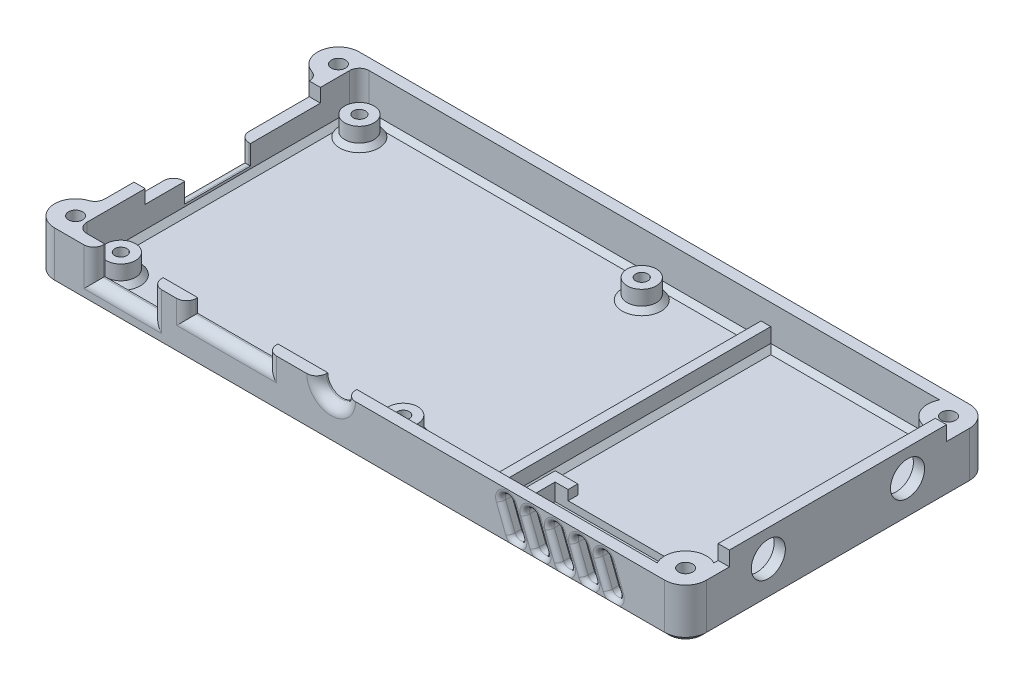
SolidWorks part; units mm, degrees
ref_plane "Front Plane" through (0, 0, 0) normal (0, 0, 1) x (1, 0, 0)
ref_plane "Top Plane" through (0, 0, 0) normal (0, 1, 0) x (1, 0, 0)
ref_plane "Right Plane" through (0, 0, 0) normal (1, 0, 0) x (0, 0, -1)
sketch "Sketch1" plane through (0, 0, 0) normal (0, 1, 0) x (1, 0, 0)
  line L0 (-71.5618, 3.106) -> (51.4382, 3.106) construction
  line L1 (-71.5618, 31.106) -> (51.4382, 31.106)
  line L2 (-71.5618, 31.106) -> (-71.5618, -24.894)
  line L3 (-71.5618, -24.894) -> (51.4382, -24.894)
  line L4 (51.4382, 31.106) -> (51.4382, -24.894)
  line L5 (-60.6618, -24.894) -> (-60.6618, -31.6828) construction
  line L6 (-68.0618, 27.606) -> (-10.0618, 27.606)
  line L7 (-68.0618, 27.606) -> (-68.0618, -21.394)
  line L8 (-68.0618, -21.394) -> (-10.0618, -21.394)
  line L9 (-10.0618, 27.606) -> (-10.0618, -21.394)
  line L10 (-39.5618, -24.894) -> (-39.5618, -31.6828) construction
  line L11 (-18.0618, -24.894) -> (-18.0618, -31.6828) construction
  line L12 (-65.4118, -26.5648) -> (-55.9118, -26.5648) construction
  line L13 (-48.0618, -26.5648) -> (-31.0618, -26.5648) construction
  line L14 (-22.0618, -26.5648) -> (-14.0618, -26.5648) construction
  line L15 (-72.5618, 9.606) -> (-72.5618, -3.394) construction
  line L16 (-71.5618, 3.106) -> (-72.5618, 3.106) construction
  dimension "D1" = 123
  dimension "D2" = 56
  dimension "D3" = 49
  dimension "D4" = 58
  dimension "D5" = 3.5
  dimension "D6" = 3.5
  dimension "D7" = 10.9
  dimension "D8" = 32
  dimension "D9" = 53.5
  dimension "D10" = 2
  dimension "D11" = 13
  dimension "D12" = 9.5
  dimension "D13" = 17
  dimension "D14" = 8
sketch "Sketch3" plane through (0, 0, 0) normal (0, 1, 0) x (1, 0, 0)
  line L4 (54.7382, 34.406) -> (-74.8618, 34.406)
  line L5 (-74.8618, 34.406) -> (-74.8618, -28.194)
  line L6 (-74.8618, -28.194) -> (54.7382, -28.194)
  line L7 (54.7382, -28.194) -> (54.7382, 34.406)
  line L8 (52.4382, 32.106) -> (-72.5618, 32.106)
  line L9 (52.4382, -25.894) -> (52.4382, 32.106)
  line L10 (-72.5618, -25.894) -> (52.4382, -25.894)
  line L11 (-72.5618, 32.106) -> (-72.5618, -25.894)
  line L12 (52.4382, 32.106) -> (-72.5618, 32.106)
  line L13 (52.4382, -25.894) -> (52.4382, 32.106)
  line L14 (-72.5618, -25.894) -> (52.4382, -25.894)
  line L15 (-72.5618, 32.106) -> (-72.5618, -25.894)
  line L16 (-10.0618, 3.106) -> (-10.0618, 34.406) construction
  line L17 (-71.5618, 3.106) -> (51.4382, 3.106) construction
  line L20 (-74.8618, 3.106) -> (52.7382, 3.106) construction
  line L25 (54.7382, -28.194) -> (54.7382, 34.406) construction
  line L26 (52.4382, -25.894) -> (52.4382, 32.106) construction
  dimension "D1" = 1
  dimension "D2" = 2.3
extrude "Boss-Extrude1" add sketch "Sketch3" along normal blind 10.3
sketch "Sketch5" plane through (0, 0, 0) normal (0, 1, 0) x (1, 0, 0)
  line L1 (-72.5618, 32.106) -> (52.4382, 32.106)
  line L2 (-72.5618, 32.106) -> (-72.5618, -25.894)
  line L3 (-72.5618, -25.894) -> (52.4382, -25.894)
  line L4 (52.4382, 32.106) -> (52.4382, -25.894)
extrude "Boss-Extrude2" add sketch "Sketch5" along normal blind 2
sketch "Sketch6" plane through (0, 2, 0) normal (0, 1, 0) x (1, 0, 0)
  circle A0 centre (-68.0618, 27.606) radius 3
  circle A1 centre (-68.0618, -21.394) radius 3
  circle A2 centre (-10.0618, -21.394) radius 3
  circle A3 centre (-10.0618, 27.606) radius 3
extrude "Boss-Extrude3" add sketch "Sketch6" along normal blind 4
hole_wizard "Ø2.5 (2.5) Diameter Hole1" positions "Sketch8" profile "Sketch9" hole size "Ø2.5" standard "ANSI Metric"
sketch "Sketch8" plane through (0, 6, 0) normal (0, 1, 0) x (1, 0, 0)
  point P0 (-68.0618, 27.606)
  point P3 (-10.0618, 27.606)
  point P6 (-10.0618, -21.394)
  point P9 (-68.0618, -21.394)
sketch "Sketch9" plane through (-68.0618, 6, -27.606) normal (1, 0, 0) x (0, 0, 1)
  line L0 (0, 0) -> (0, 8.7511)
  line L1 (0, 8.7511) -> (1.25, 8)
  line L2 (1.25, 8) -> (1.25, 0)
  line L5 (1.25, 0) -> (0, 0)
  line L10 (0, 8.7511) -> (-1.25, 8) construction
  line L11 (0, -6.35) -> (0, 107.95) construction
  dimension "Hole Dia." = 2.5
  dimension "Hole Depth" = 8
  dimension "Drill Angle" = 118
sketch "Sketch10" plane through (0, 2, 0) normal (0, 1, 0) x (1, 0, 0)
  line L0 (52.4382, 32.106) -> (-72.5618, 32.106) construction
  line L1 (9.9382, 32.106) -> (11.9382, 32.106)
  line L2 (9.9382, 32.106) -> (9.9382, -25.894)
  line L3 (9.9382, -25.894) -> (11.9382, -25.894)
  line L4 (11.9382, 32.106) -> (11.9382, -25.894)
  line L5 (-72.5618, -25.894) -> (52.4382, -25.894) construction
  line L6 (-10.0618, 27.606) -> (-10.0618, -21.394) construction
  dimension "D1" = 2
  dimension "D2" = 20
extrude "Boss-Extrude4" add sketch "Sketch10" along normal blind 4
sketch "Sketch11" plane through (0, 0, 28.194) normal (0, 0, 1) x (1, 0, 0)
  line L0 (-74.8618, 10.3) -> (-74.8618, 0) construction
  line L1 (-66.8618, 10.3) -> (-54.8618, 10.3)
  line L2 (-66.8618, 10.3) -> (-66.8618, 4.5)
  line L3 (-66.8618, 4.5) -> (-54.8618, 4.5)
  line L4 (-54.8618, 10.3) -> (-54.8618, 4.5)
  line L5 (-74.8618, 0) -> (54.7382, 0) construction
  line L6 (-60.8618, 10.3) -> (-60.6618, 0) construction
  line L7 (-65.4118, 0) -> (-55.9118, 0) construction
  line L9 (-47.778, 10.3) -> (-31.278, 10.3)
  line L10 (-47.778, 10.3) -> (-47.778, 7.5)
  line L11 (-47.778, 7.5) -> (-31.278, 7.5)
  line L12 (-31.278, 10.3) -> (-31.278, 7.5)
  line L13 (-68.0618, 0) -> (-10.0618, 0) construction
  line L14 (-39.5618, 0) -> (-39.528, 10.3) construction
  line L15 (-48.0618, 0) -> (-31.0618, 0) construction
  line L16 (-18.0618, 0) -> (-18.0618, 10.3) construction
  line L17 (-22.0618, 0) -> (-14.0618, 0) construction
  line L18 (-74.8618, 10.3) -> (54.7382, 10.3) construction
  circle A0 centre (-18.0618, 10.3) radius 3
  dimension "D5" = 6
  dimension "D1" = 4.5
  dimension "D2" = 12
  dimension "D3" = 7.5
  dimension "D4" = 16.5
  dimension "D6" = 8
extrude "Cut-Extrude1" cut sketch "Sketch11" against normal up to next
sketch "Sketch12" plane through (-74.8618, 0, 0) normal (-1, 0, 0) x (0, 0, 1)
  line L0 (-3.106, 0) -> (-3.106, 10.3) construction
  line L1 (-27.606, 0) -> (21.394, 0) construction
  line L2 (-34.406, 10.3) -> (28.194, 10.3) construction
  line L4 (-9.7329, 10.3) -> (3.7671, 10.3)
  line L5 (-9.7329, 10.3) -> (-9.7329, 3.5)
  line L6 (-9.7329, 3.5) -> (3.7671, 3.5)
  line L7 (3.7671, 10.3) -> (3.7671, 3.5)
  line L8 (-24.106, 10.3) -> (11.894, 10.3)
  line L9 (-24.106, 10.3) -> (-24.106, 7.5)
  line L10 (-24.106, 7.5) -> (11.894, 7.5)
  line L11 (11.894, 10.3) -> (11.894, 7.5)
  dimension "D1" = 13.5
  dimension "D2" = 3.5
  dimension "D3" = 7.5
  dimension "D4" = 36
extrude "Cut-Extrude2" cut sketch "Sketch12" against normal up to next contours L10 L11 L8 L9 | L7 L6 L5 L4
fillet "Fillet6" radius 2 1 edges at (52.4382, 6.15, -32.106)
fillet "Fillet8" radius 2 2 edges at (-72.5618, 6.15, 25.894) (-72.5618, 6.15, -32.106)
chamfer "Chamfer1" distance 1 angle 45 4 edges at (-68.0618, 2, 24.394) (-10.0618, 2, 24.394) (-10.0618, 2, -24.606) (-68.0618, 2, -24.606)
fillet "Fillet9" radius 2 9 edges at (-74.8618, 5.5, -9.7329) (-74.8618, 3.5, -2.9829) (-74.8618, 5.5, 3.7671) (-18.0618, 7.3, 28.194) (-31.278, 8.9, 28.194) (-47.778, 8.9, 28.194) (-39.528, 7.5, 28.194) (-54.8618, 7.4, 28.194) (-60.8618, 4.5, 28.194)
sketch "Sketch13" plane through (54.7382, 0, -61.1442) normal (1, 0, 0) x (0, 0, -1)
  line L0 (-89.3382, 10.3) -> (-89.3382, 0) construction
  line L1 (-26.7382, 10.3) -> (-26.7382, 0) construction
  circle A0 centre (-72.3382, 7.7223) radius 3.5
  circle A1 centre (-43.7382, 7.7223) radius 3.5
  dimension "D1" = 17
  dimension "D2" = 17
sketch "Sketch17" plane through (0, 0, 0) normal (0, 1, 0) x (1, 0, 0)
  line L0 (-74.8618, 34.406) -> (-74.8618, 24.106) construction
  line L1 (-74.8618, 34.406) -> (-74.8618, 25.806)
  line L2 (-74.8618, 25.806) -> (-74.659, 25.9406)
  line L3 (-74.8618, -19.594) -> (-74.8618, -28.194)
  line L4 (-74.8618, -28.194) -> (-74.659, -28.0594)
  arc A0 (-74.8618, -19.594) -> (-74.8618, -28.194) centre (-74.8618, -23.894) ccw
  arc A1 (-74.8618, 34.406) -> (-74.8618, 25.806) centre (-74.8618, 30.106) ccw
extrude "Boss-Extrude6" add sketch "Sketch17" along normal up to vertex (10.3 mm away) contours L1 A1 | L3 A0 region at (-76.6867, 0, -30.106) region at (-76.6867, 0, 23.894) up to point (-74.8618, 10.3, 28.194)
hole_wizard "Ø2.9 (2.9) Diameter Hole2" positions "Sketch19" profile "Sketch18" hole size "Ø2.9" standard "ANSI Metric" end condition up to next
sketch "Sketch19" plane through (0, 10.3, 0) normal (0, 1, 0) x (1, 0, 0)
  point P0 (-74.8618, 30.106)
sketch "Sketch18" plane through (-74.8618, 10.3, -30.106) normal (1, 0, 0) x (0, 0, 1)
  line L0 (0, 0) -> (0, 10.3)
  line L1 (0, 10.3) -> (1.45, 10.3)
  line L2 (1.45, 10.3) -> (1.45, 0)
  line L5 (1.45, 0) -> (0, 0)
  line L11 (0, -6.35) -> (0, 107.95) construction
  dimension "Thru Hole Dia." = 2.9
  dimension "Thru Hole Depth" = 10.3
hole_wizard "Ø2.9 (2.9) Diameter Hole1" positions "Sketch21" profile "Sketch20" hole size "Ø2.9" standard "ANSI Metric" end condition up to next
sketch "Sketch21" plane through (0, 10.3, 0) normal (0, 1, 0) x (1, 0, 0)
  point P0 (-74.8618, -23.894)
sketch "Sketch20" plane through (-74.8618, 10.3, 23.894) normal (1, 0, 0) x (0, 0, 1)
  line L0 (0, 0) -> (0, 10.3)
  line L1 (0, 10.3) -> (1.45, 10.3)
  line L2 (1.45, 10.3) -> (1.45, 0)
  line L5 (1.45, 0) -> (0, 0)
  line L11 (0, -6.35) -> (0, 107.95) construction
  dimension "Thru Hole Dia." = 2.9
  dimension "Thru Hole Depth" = 10.3
sketch "Sketch24" plane through (0, 2, 0) normal (0, 1, 0) x (1, 0, 0)
  line L0 (11.9382, 3.106) -> (61.5789, 3.106) construction
  line L1 (11.9382, -25.894) -> (11.9382, 32.106) construction
  line L2 (54.7382, -28.194) -> (54.7382, 34.406) construction
  circle A0 centre (50.4382, -23.894) radius 4.3
  circle A1 centre (50.4382, 30.106) radius 4.3
  dimension "D1" = 4.3
extrude "Boss-Extrude7" add sketch "Sketch24" along normal up to surface (8.3 mm away) up to face at (-74.8618, 10.3, 25.344)
hole_wizard "Ø2.9 (2.9) Diameter Hole5" positions "Sketch31" profile "Sketch30" hole size "Ø2.9" standard "ANSI Metric" end condition up to next
sketch "Sketch31" plane through (0, 10.3, 0) normal (0, 1, 0) x (1, 0, 0)
  point P0 (50.4382, -23.894)
sketch "Sketch30" plane through (50.4382, 10.3, 23.894) normal (1, 0, 0) x (0, 0, 1)
  line L0 (0, 0) -> (0, 10.3)
  line L1 (0, 10.3) -> (1.45, 10.3)
  line L2 (1.45, 10.3) -> (1.45, 0)
  line L5 (1.45, 0) -> (0, 0)
  line L11 (0, -6.35) -> (0, 107.95) construction
  dimension "Thru Hole Dia." = 2.9
  dimension "Thru Hole Depth" = 10.3
hole_wizard "Ø2.9 (2.9) Diameter Hole4" positions "Sketch28" profile "Sketch27" hole size "Ø2.9" standard "ANSI Metric" end condition up to next
sketch "Sketch28" plane through (0, 10.3, 0) normal (0, 1, 0) x (1, 0, 0)
  point P0 (50.4382, 30.106)
sketch "Sketch27" plane through (50.4382, 10.3, -30.106) normal (1, 0, 0) x (0, 0, 1)
  line L0 (0, 0) -> (0, 10.3)
  line L1 (0, 10.3) -> (1.45, 10.3)
  line L2 (1.45, 10.3) -> (1.45, 0)
  line L5 (1.45, 0) -> (0, 0)
  line L11 (0, -6.35) -> (0, 107.95) construction
  dimension "Thru Hole Dia." = 2.9
  dimension "Thru Hole Depth" = 10.3
fillet "Fillet10" radius 4.3 1 edges at (54.7382, 5.15, -34.406)
fillet "Fillet18" radius 2 2 edges at (-74.8618, 5.15, 19.594) (-74.8618, 5.15, -25.806)
chamfer "Chamfer3" distance 1 angle 45 9 edges at (53.4788, 0, -33.1466) (-12.2118, 0, -34.406) (54.7382, 0, -0.956) (-79.1058, 0, -30.7975) (-75.2385, 0, -25.3002) (-74.8618, 0, -3.106) (-75.2385, 0, 19.0883) (-79.1058, 0, 24.5855) (-10.0618, 0, 28.194)
fillet "Fillet19" radius 2 1 edges at (-66.8618, 6.4, 28.194)
fillet "Fillet20" radius 4.3 1 edges at (54.7382, 5.65, 28.194)
chamfer "Chamfer5" distance 1 angle 45 8 edges at (-72.5618, 2, -3.106) (-71.976, 2, 25.3082) (-71.976, 2, -31.5202) (-30.3118, 2, 25.894) (-30.3118, 2, -32.106) (9.9382, 2, -3.106) (11.9382, 2, -3.106) (29.2849, 2, -32.106)
chamfer "Chamfer6" distance 1 angle 45 1 edges at (52.4382, 2, -3.106)
sketch "Sketch29" plane through (0, 10.3, 0) normal (0, 1, 0) x (1, 0, 0)
  line L0 (52.4382, -20.0874) -> (52.4382, 26.2994) construction
  line L1 (52.4382, 25.406) -> (54.7382, 25.406)
  line L2 (52.4382, 25.406) -> (52.4382, -19.194)
  line L3 (52.4382, -19.194) -> (54.7382, -19.194)
  line L4 (54.7382, 25.406) -> (54.7382, -19.194)
  line L5 (54.7382, -23.894) -> (54.7382, 30.106) construction
  line L6 (50.4382, 34.406) -> (-74.8618, 34.406) construction
  line L7 (-13.0618, -28.194) -> (50.4382, -28.194) construction
  dimension "D1" = 9
  dimension "D2" = 9
extrude "Boss-Extrude8" add sketch "Sketch29" along normal blind 3
extrude "Cut-Extrude3" cut sketch "Sketch13" against normal up to next
sketch "Sketch32" plane through (0, 2, 0) normal (0, 1, 0) x (1, 0, 0)
  line L0 (12.9382, -25.894) -> (46.6317, -25.894) construction
  line L1 (15.4382, -15.694) -> (45.5382, -15.694)
  line L2 (15.4382, -15.694) -> (15.4382, -25.894)
  line L3 (15.4382, -25.894) -> (45.5382, -25.894)
  line L4 (45.5382, -15.694) -> (45.5382, -25.894)
  line L5 (-72.5618, -23.894) -> (-72.5618, 30.106) construction
  dimension "D1" = 10.2
  dimension "D2" = 30.1
  dimension "D3" = 88
extrude "Cut-Extrude4" cut sketch "Sketch32" against normal blind 1.5
sketch "Sketch33" plane through (0, 2, 0) normal (0, 1, 0) x (1, 0, 0)
  line L0 (15.4382, -15.694) -> (15.4382, -25.894)
  line L2 (15.4382, -25.894) -> (13.4382, -25.894)
  line L3 (12.9382, -25.894) -> (15.4382, -25.894) construction
  line L4 (47.5382, -13.694) -> (47.5382, -20.8822)
  line L5 (47.5382, -20.8822) -> (45.5382, -20.8822)
  line L6 (45.5382, -25.894) -> (45.5382, -20.7012) construction
  line L7 (45.5382, -20.8822) -> (45.5382, -15.694)
  line L8 (30.4882, -15.694) -> (30.4882, -23.4127) construction
  line L9 (45.5382, -15.694) -> (15.4382, -15.694) construction
  line L10 (18.1083, -13.694) -> (18.1083, -15.694)
  line L11 (42.8681, -13.694) -> (42.8681, -15.694)
  line L12 (13.4382, -13.694) -> (13.4382, -27.894)
  line L13 (13.4382, -27.894) -> (47.5382, -27.894)
  line L14 (47.5382, -27.894) -> (47.5382, -13.694)
  line L15 (47.5382, -13.694) -> (13.4382, -13.694)
  line L16 (13.4382, -13.694) -> (13.4382, -25.894)
  line L17 (45.5382, -15.694) -> (42.8681, -15.694)
  line L19 (47.5382, -13.694) -> (42.8681, -13.694)
  line L20 (18.1083, -13.694) -> (13.4382, -13.694)
  line L21 (18.1083, -15.694) -> (15.4382, -15.694)
  dimension "D1" = 2
extrude "Boss-Extrude9" add sketch "Sketch33" along normal blind 2
sketch "Sketch34" plane through (0, 0, 28.194) normal (0, 0, 1) x (1, 0, 0)
  line L0 (17.9748, 7.7443) -> (19.8911, 2.8029) construction
  line L1 (19.1402, 8.1963) -> (21.0565, 3.2549)
  line L2 (16.8093, 7.2924) -> (18.7256, 2.3509)
  line L3 (22.9748, 7.7443) -> (24.8911, 2.8029) construction
  line L4 (24.1402, 8.1963) -> (26.0565, 3.2549)
  line L5 (21.8093, 7.2924) -> (23.7256, 2.3509)
  line L6 (27.9748, 7.7443) -> (29.8911, 2.8029) construction
  line L7 (29.1402, 8.1963) -> (31.0565, 3.2549)
  line L8 (26.8093, 7.2924) -> (28.7256, 2.3509)
  line L9 (32.9748, 7.7443) -> (34.8911, 2.8029) construction
  line L10 (34.1402, 8.1963) -> (36.0565, 3.2549)
  line L11 (31.8093, 7.2924) -> (33.7256, 2.3509)
  line L12 (37.9748, 7.7443) -> (39.8911, 2.8029) construction
  line L13 (39.1402, 8.1963) -> (41.0565, 3.2549)
  line L14 (36.8093, 7.2924) -> (38.7256, 2.3509)
  arc A0 (19.1402, 8.1963) -> (16.8093, 7.2924) centre (17.9748, 7.7443) ccw
  arc A1 (18.7256, 2.3509) -> (21.0565, 3.2549) centre (19.8911, 2.8029) ccw
  arc A2 (24.1402, 8.1963) -> (21.8093, 7.2924) centre (22.9748, 7.7443) ccw
  arc A3 (23.7256, 2.3509) -> (26.0565, 3.2549) centre (24.8911, 2.8029) ccw
  arc A4 (29.1402, 8.1963) -> (26.8093, 7.2924) centre (27.9748, 7.7443) ccw
  arc A5 (28.7256, 2.3509) -> (31.0565, 3.2549) centre (29.8911, 2.8029) ccw
  arc A6 (34.1402, 8.1963) -> (31.8093, 7.2924) centre (32.9748, 7.7443) ccw
  arc A7 (33.7256, 2.3509) -> (36.0565, 3.2549) centre (34.8911, 2.8029) ccw
  arc A8 (39.1402, 8.1963) -> (36.8093, 7.2924) centre (37.9748, 7.7443) ccw
  arc A9 (38.7256, 2.3509) -> (41.0565, 3.2549) centre (39.8911, 2.8029) ccw
  point P2 (18.9329, 5.2736)
  point P9 (23.9329, 5.2736)
  point P16 (28.9329, 5.2736)
  point P23 (33.9329, 5.2736)
  point P30 (38.9329, 5.2736)
extrude "Cut-Extrude5" cut sketch "Sketch34" against normal up to next
fillet "Fillet21" radius 1 20 edges at (37.5228, 8.9098, 28.194) (40.0983, 5.7256, 28.194) (40.343, 1.6375, 28.194) (32.5228, 8.9098, 28.194) (35.0983, 5.7256, 28.194) (35.343, 1.6375, 28.194) (27.5228, 8.9098, 28.194) (30.0983, 5.7256, 28.194) (30.343, 1.6375, 28.194) (22.5228, 8.9098, 28.194) (25.0983, 5.7256, 28.194) (25.343, 1.6375, 28.194) (17.5228, 8.9098, 28.194) (20.0983, 5.7256, 28.194) (20.343, 1.6375, 28.194) (37.7675, 4.8217, 28.194) (32.7675, 4.8217, 28.194) (27.7675, 4.8217, 28.194) (22.7675, 4.8217, 28.194) (17.7675, 4.8217, 28.194)
chamfer "Chamfer7" distance 1 angle 45 1 edges at (53.4788, 0, 26.9346)
